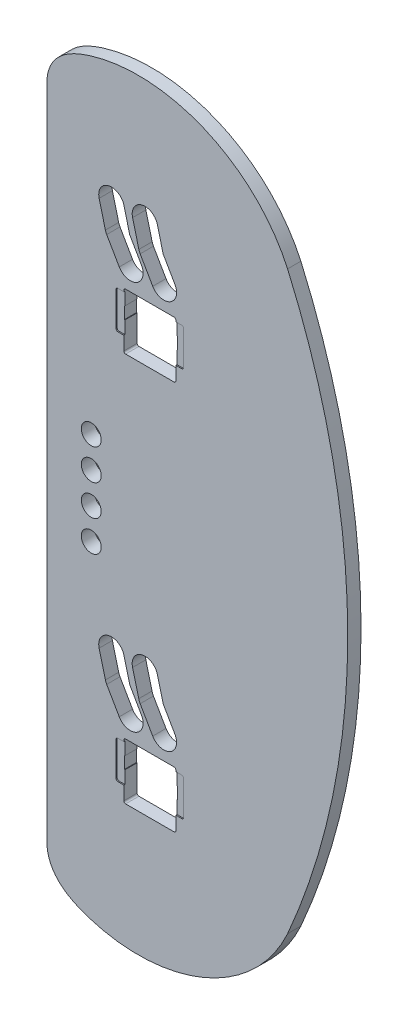
SolidWorks part; units mm, degrees
material "Pine"
ref_plane "Front Plane" through (0, 0, 0) normal (0, 0, 1) x (1, 0, 0)
ref_plane "Top Plane" through (0, 0, 0) normal (0, 1, 0) x (1, 0, 0)
ref_plane "Right Plane" through (0, 0, 0) normal (1, 0, 0) x (0, 0, -1)
sketch "Sketch1" plane through (0, 0, 0) normal (0, 1, 0) x (1, 0, 0)
  line L0 (-92.9216, 89.0184) -> (669.0784, 89.0184)
  line L1 (669.0784, 89.0184) -> (669.0784, 419.2184)
  line L2 (-92.9216, 89.0184) -> (-92.9216, 419.2184)
  line L5 (110.2784, 495.4184) -> (465.8784, 495.4184)
  line L8 (110.2784, 495.4184) -> (-92.9216, 419.2184)
  line L9 (465.8784, 495.4184) -> (669.0784, 419.2184)
  line L10 (-92.9216, 495.4184) -> (669.0784, 495.4184) construction
sketch "Sketch2" plane through (0, 0, 0) normal (0, 0, 1) x (1, 0, 0)
  line L95 (1361.0966, 1819.7347) -> (1361.0966, 996.3635)
  arc A0 (1691.2966, 1027.0491) -> (1691.2966, 1789.0491) centre (733.0004, 1408.0491) ccw
  spline S0 degree 3 poles (1691.2966, 1027.0491) (1656.7077, 922.0591) (1371.3251, 886.2968) (1361.0966, 996.3635) knots 0 0 0 0 7.629784 7.629784 7.629784 7.629784
  spline S1 degree 3 poles (1691.2966, 1789.0491) (1656.7629, 1894.0573) (1371.3251, 1929.8013) (1361.0966, 1819.7347) knots 0 0 0 0 7.638295 7.638295 7.638295 7.638295
sketch "Sketch5" plane through (0, 0, 0) normal (0, 0, 1) x (1, 0, 0)
  line L0 (1361.0966, 1819.7347) -> (1361.0966, 996.3635)
  line L1 (1361.0966, 1789.0491) -> (1361.0966, 1027.0491)
  line L2 (1540.0357, 1006.8697) -> (1540.0357, 1016.3947)
  line L3 (1486.0607, 1097.3572) -> (1486.0607, 1006.8697) construction
  line L4 (1486.0607, 1102.1197) -> (1486.0607, 1092.5947)
  line L5 (1540.0357, 1006.8697) -> (1540.0357, 1097.3572) construction
  line L6 (1544.7982, 1102.1197) -> (1481.2982, 1102.1197) construction
  line L7 (1486.0607, 1006.8697) -> (1540.0357, 1006.8697)
  line L8 (1479.7107, 1016.3947) -> (1546.3857, 1016.3947)
  line L9 (1546.3857, 1016.3947) -> (1546.3857, 1092.5947)
  line L10 (1546.3857, 1092.5947) -> (1479.7107, 1092.5947)
  line L11 (1479.7107, 1016.3947) -> (1479.7107, 1092.5947)
  line L12 (1540.0357, 1548.8399) -> (1540.0357, 1558.3649)
  line L13 (1486.0607, 1548.8399) -> (1540.0357, 1548.8399)
  line L14 (1546.3857, 1634.5649) -> (1479.7107, 1634.5649)
  line L15 (1486.0607, 1644.0899) -> (1486.0607, 1634.5649)
  line L16 (1479.7107, 1558.3649) -> (1479.7107, 1634.5649)
  line L17 (1540.0357, 1644.0899) -> (1486.0607, 1644.0899)
  line L18 (1479.7107, 1558.3649) -> (1546.3857, 1558.3649)
  line L19 (1546.3857, 1558.3649) -> (1546.3857, 1634.5649)
  line L20 (1540.0357, 1092.5947) -> (1540.0357, 1102.1197)
  line L21 (1486.0607, 1016.3947) -> (1486.0607, 1006.8697)
  line L22 (1540.0357, 1634.5649) -> (1540.0357, 1644.0899)
  line L23 (1486.0607, 1558.3649) -> (1486.0607, 1548.8399)
  line L95 (1361.0966, 1819.7347) -> (1361.0966, 996.3635)
  line L115 (1540.0357, 1102.1197) -> (1486.0607, 1102.1197)
  line L199 (1363.2449, 1823.8418) -> (1361.0966, 1819.7347)
  line L200 (1361.0966, 1819.7347) -> (1361.7967, 1824.3165)
  line L201 (1361.7967, 1824.3165) -> (1363.2449, 1823.8418)
  line L202 (1540.0357, 1097.3572) -> (1486.0607, 1097.3572) construction
  line L203 (1481.2982, 1102.1197) -> (1481.2982, 1006.8697) construction
  line L204 (1544.7982, 1006.8697) -> (1544.7982, 1102.1197) construction
  arc A0 (1691.2966, 1027.0491) -> (1691.2966, 1789.0491) centre (733.0004, 1408.0491) ccw
  circle A1 centre (1506.0488, 1194.0197) radius 15.875
  circle A2 centre (1515.0488, 1159.0198) radius 15.875
  circle A3 centre (1533.0488, 1127.7698) radius 15.875
  circle A4 centre (1467.0488, 1159.0198) radius 15.875
  circle A5 centre (1485.0488, 1127.7698) radius 15.875
  circle A6 centre (1458.0488, 1194.0197) radius 15.875
  circle A7 centre (1513.0482, 1054.4947) radius 12
  circle A8 centre (1506.0488, 1735.9899) radius 15.875
  circle A9 centre (1515.0488, 1700.99) radius 15.875
  circle A10 centre (1533.0488, 1669.74) radius 15.875
  circle A11 centre (1467.0488, 1700.99) radius 15.875
  circle A12 centre (1485.0488, 1669.74) radius 15.875
  circle A13 centre (1458.0488, 1735.9899) radius 15.875
  circle A15 centre (1483.5084, 1375.1967) radius 12
  circle A16 centre (1483.9827, 1438.6917) radius 12
  circle A17 centre (1551.8392, 1408.0266) radius 29.9999
  circle A18 centre (1409.3368, 1408.0266) radius 15.9995
  circle A19 centre (1513.0482, 1596.4649) radius 12
  arc A30 (1539.4945, 1725.9331) -> (1482.0488, 1761.3623) centre (1506.0488, 1735.9899) ccw
  arc A32 (1549.9668, 1700.2938) -> (1539.4945, 1725.9331) centre (1515.0488, 1700.99) ccw
  arc A41 (1509.0488, 1644.3676) -> (1549.9668, 1700.2938) centre (1533.0488, 1669.74) ccw
  arc A46 (1450.1308, 1670.4362) -> (1509.0488, 1644.3676) centre (1485.0488, 1669.74) ccw
  arc A47 (1433.6031, 1711.0467) -> (1450.1308, 1670.4362) centre (1467.0488, 1700.99) ccw
  arc A50 (1482.0488, 1761.3623) -> (1433.6031, 1711.0467) centre (1458.0488, 1735.9899) ccw
  arc A64 (1509.0488, 1102.3974) -> (1549.9668, 1158.3235) centre (1533.0488, 1127.7698) ccw
  arc A66 (1450.1308, 1128.466) -> (1509.0488, 1102.3974) centre (1485.0488, 1127.7698) ccw
  arc A68 (1433.6031, 1169.0765) -> (1450.1308, 1128.466) centre (1467.0488, 1159.0198) ccw
  arc A70 (1539.4945, 1183.9629) -> (1482.0488, 1219.3921) centre (1506.0488, 1194.0197) ccw
  arc A72 (1549.9668, 1158.3235) -> (1539.4945, 1183.9629) centre (1515.0488, 1159.0198) ccw
  arc A73 (1482.0488, 1219.3921) -> (1433.6031, 1169.0765) centre (1458.0488, 1194.0197) ccw
  arc A86 (1474.249, 1382.8299) -> (1489.0021, 1364.5282) centre (1483.5084, 1375.1967) ccw
  arc A89 (1488.8753, 1449.649) -> (1474.6166, 1431.19) centre (1483.9827, 1438.6917) ccw
  arc A97 (1557.861, 1378.6372) -> (1557.0728, 1437.5665) centre (1551.8392, 1408.0266) ccw
  arc A99 (1420.1657, 1419.8299) -> (1400.5179, 1421.402) centre (1409.3362, 1408.0491) ccw
  arc A100 (1402.6554, 1393.5084) -> (1419.641, 1395.8067) centre (1409.3362, 1408.0491) ccw
  spline S0 degree 3 poles (1691.2966, 1027.0491) (1656.7077, 922.0591) (1371.3251, 886.2968) (1361.0966, 996.3635) knots 0 0 0 0 7.629784 7.629784 7.629784 7.629784
  spline S1 degree 3 poles (1691.2966, 1789.0491) (1656.7629, 1894.0573) (1371.3251, 1929.8013) (1361.0966, 1819.7347) knots 0 0 0 0 7.638295 7.638295 7.638295 7.638295
  dimension "D1" = 4.7625
sketch "Sketch8" plane through (0, 0, 0) normal (0, 0, 1) x (1, 0, 0)
  line L2 (1540.0357, 1006.8697) -> (1540.0357, 1016.3947)
  line L3 (1486.0607, 1097.3572) -> (1486.0607, 1006.8697) construction
  line L4 (1486.0607, 1102.1197) -> (1486.0607, 1092.5947)
  line L5 (1540.0357, 1006.8697) -> (1540.0357, 1097.3572) construction
  line L6 (1544.7982, 1102.1197) -> (1481.2982, 1102.1197) construction
  line L7 (1486.0607, 1006.8697) -> (1540.0357, 1006.8697)
  line L8 (1479.7107, 1016.3947) -> (1546.3857, 1016.3947)
  line L9 (1546.3857, 1016.3947) -> (1546.3857, 1092.5947)
  line L10 (1546.3857, 1092.5947) -> (1479.7107, 1092.5947)
  line L11 (1479.7107, 1016.3947) -> (1479.7107, 1092.5947)
  line L12 (1540.0357, 1548.8399) -> (1540.0357, 1558.3649)
  line L13 (1486.0607, 1548.8399) -> (1540.0357, 1548.8399)
  line L14 (1546.3857, 1634.5649) -> (1479.7107, 1634.5649)
  line L15 (1486.0607, 1644.0899) -> (1486.0607, 1634.5649)
  line L16 (1479.7107, 1558.3649) -> (1479.7107, 1634.5649)
  line L17 (1540.0357, 1644.0899) -> (1486.0607, 1644.0899)
  line L18 (1479.7107, 1558.3649) -> (1546.3857, 1558.3649)
  line L19 (1546.3857, 1558.3649) -> (1546.3857, 1634.5649)
  line L20 (1540.0357, 1092.5947) -> (1540.0357, 1102.1197)
  line L21 (1486.0607, 1016.3947) -> (1486.0607, 1006.8697)
  line L22 (1540.0357, 1634.5649) -> (1540.0357, 1644.0899)
  line L23 (1486.0607, 1558.3649) -> (1486.0607, 1548.8399)
  line L95 (1361.0966, 1819.7347) -> (1361.0966, 996.3635)
  line L115 (1540.0357, 1102.1197) -> (1486.0607, 1102.1197)
  line L202 (1540.0357, 1097.3572) -> (1486.0607, 1097.3572) construction
  line L203 (1481.2982, 1102.1197) -> (1481.2982, 1006.8697) construction
  line L204 (1544.7982, 1006.8697) -> (1544.7982, 1102.1197) construction
  arc A0 (1691.2966, 1027.0491) -> (1691.2966, 1789.0491) centre (733.0004, 1408.0491) ccw
  circle A1 centre (1506.0488, 1194.0197) radius 15.875
  circle A2 centre (1515.0488, 1159.0198) radius 15.875
  circle A3 centre (1533.0488, 1127.7698) radius 15.875
  circle A4 centre (1467.0488, 1159.0198) radius 15.875
  circle A5 centre (1485.0488, 1127.7698) radius 15.875
  circle A6 centre (1458.0488, 1194.0197) radius 15.875
  circle A7 centre (1513.0482, 1054.4947) radius 12
  circle A8 centre (1506.0488, 1735.9899) radius 15.875
  circle A9 centre (1515.0488, 1700.99) radius 15.875
  circle A10 centre (1533.0488, 1669.74) radius 15.875
  circle A11 centre (1467.0488, 1700.99) radius 15.875
  circle A12 centre (1485.0488, 1669.74) radius 15.875
  circle A13 centre (1458.0488, 1735.9899) radius 15.875
  circle A15 centre (1483.5084, 1375.1967) radius 12
  circle A16 centre (1483.9827, 1438.6917) radius 12
  circle A17 centre (1551.8392, 1408.0266) radius 29.9999
  circle A18 centre (1409.3368, 1408.0266) radius 15.9995
  circle A19 centre (1513.0482, 1596.4649) radius 12
  arc A30 (1539.4945, 1725.9331) -> (1482.0488, 1761.3623) centre (1506.0488, 1735.9899) ccw
  arc A32 (1549.9668, 1700.2938) -> (1539.4945, 1725.9331) centre (1515.0488, 1700.99) ccw
  arc A41 (1509.0488, 1644.3676) -> (1549.9668, 1700.2938) centre (1533.0488, 1669.74) ccw
  arc A46 (1450.1308, 1670.4362) -> (1509.0488, 1644.3676) centre (1485.0488, 1669.74) ccw
  arc A47 (1433.6031, 1711.0467) -> (1450.1308, 1670.4362) centre (1467.0488, 1700.99) ccw
  arc A50 (1482.0488, 1761.3623) -> (1433.6031, 1711.0467) centre (1458.0488, 1735.9899) ccw
  arc A64 (1509.0488, 1102.3974) -> (1549.9668, 1158.3235) centre (1533.0488, 1127.7698) ccw
  arc A66 (1450.1308, 1128.466) -> (1509.0488, 1102.3974) centre (1485.0488, 1127.7698) ccw
  arc A68 (1433.6031, 1169.0765) -> (1450.1308, 1128.466) centre (1467.0488, 1159.0198) ccw
  arc A70 (1539.4945, 1183.9629) -> (1482.0488, 1219.3921) centre (1506.0488, 1194.0197) ccw
  arc A72 (1549.9668, 1158.3235) -> (1539.4945, 1183.9629) centre (1515.0488, 1159.0198) ccw
  arc A73 (1482.0488, 1219.3921) -> (1433.6031, 1169.0765) centre (1458.0488, 1194.0197) ccw
  arc A86 (1474.249, 1382.8299) -> (1489.0021, 1364.5282) centre (1483.5084, 1375.1967) ccw
  arc A89 (1488.8753, 1449.649) -> (1474.6166, 1431.19) centre (1483.9827, 1438.6917) ccw
  arc A97 (1557.861, 1378.6372) -> (1557.0728, 1437.5665) centre (1551.8392, 1408.0266) ccw
  arc A99 (1420.1657, 1419.8299) -> (1400.5179, 1421.402) centre (1409.3362, 1408.0491) ccw
  arc A100 (1402.6554, 1393.5084) -> (1419.641, 1395.8067) centre (1409.3362, 1408.0491) ccw
  spline S0 degree 3 poles (1691.2966, 1027.0491) (1656.7077, 922.0591) (1371.3251, 886.2968) (1361.0966, 996.3635) knots 0 0 0 0 7.629784 7.629784 7.629784 7.629784
  spline S1 degree 3 poles (1691.2966, 1789.0491) (1656.7629, 1894.0573) (1371.3251, 1929.8013) (1361.0966, 1819.7347) knots 0 0 0 0 7.638295 7.638295 7.638295 7.638295
  dimension "D1" = 4.7625
sketch "Sketch9" plane through (0, 0, 0) normal (0, 0, 1) x (1, 0, 0)
  line L0 (1361.0966, 1884.2991) -> (1361.0966, 1060.9279)
  line L1 (1361.0966, 1472.6135) -> (1839.973, 1472.6135)
  circle A20 centre (1506.0488, 1272.2885) radius 12
  circle A21 centre (1515.0488, 1237.2885) radius 12
  circle A22 centre (1533.0488, 1206.0385) radius 12
  circle A23 centre (1467.0488, 1237.2885) radius 12
  circle A24 centre (1485.0488, 1206.0385) radius 12
  circle A25 centre (1458.0488, 1272.2885) radius 12
  circle A26 centre (1513.0482, 1142.2885) radius 12
  circle A27 centre (1501.6642, 1830.4221) radius 12
  circle A28 centre (1510.6642, 1795.4221) radius 12
  circle A29 centre (1528.6642, 1764.1721) radius 12
  circle A31 centre (1462.6642, 1795.4221) radius 12
  circle A33 centre (1480.6642, 1764.1721) radius 12
  circle A34 centre (1453.6642, 1830.4221) radius 12
  circle A35 centre (1508.6636, 1700.4221) radius 12
sketch "Sketch13" plane through (0, 0, 0) normal (0, 0, 1) x (1, 0, 0)
  line L0 (1439.599, 1277.0692) -> (1448.5991, 1242.0693)
  line L1 (1450.5414, 1237.3053) -> (1468.5414, 1206.0553)
  line L2 (1540.0357, 1097.2035) -> (1540.0357, 1104.1885)
  line L3 (1486.0607, 1185.151) -> (1486.0607, 1006.8697) construction
  line L4 (1486.0607, 1187.3735) -> (1486.0607, 1180.3885)
  line L5 (1540.0357, 1006.8697) -> (1540.0357, 1185.151) construction
  line L6 (1544.7982, 1189.9135) -> (1481.2982, 1189.9135) construction
  line L7 (1488.6007, 1094.6635) -> (1537.4957, 1094.6635)
  line L8 (1482.2507, 1104.1885) -> (1543.8457, 1104.1885)
  line L9 (1546.3857, 1106.7285) -> (1546.3857, 1177.8485)
  line L10 (1543.8457, 1180.3885) -> (1482.2507, 1180.3885)
  line L11 (1479.7107, 1106.7285) -> (1479.7107, 1177.8485)
  line L12 (1540.0357, 1656.0035) -> (1540.0357, 1662.9885)
  line L13 (1488.6007, 1653.4635) -> (1537.4957, 1653.4635)
  line L14 (1543.8457, 1739.1885) -> (1482.2507, 1739.1885)
  line L15 (1486.0607, 1746.1735) -> (1486.0607, 1739.1885)
  line L16 (1479.7107, 1665.5285) -> (1479.7107, 1736.6485)
  line L17 (1537.4957, 1748.7135) -> (1488.6007, 1748.7135)
  line L18 (1482.2507, 1662.9885) -> (1543.8457, 1662.9885)
  line L19 (1546.3857, 1665.5285) -> (1546.3857, 1736.6485)
  line L20 (1540.0357, 1180.3885) -> (1540.0357, 1187.3735)
  line L21 (1486.0607, 1104.1885) -> (1486.0607, 1097.2035)
  line L22 (1540.0357, 1739.1885) -> (1540.0357, 1746.1735)
  line L23 (1486.0607, 1662.9885) -> (1486.0607, 1656.0035)
  line L24 (1485.0488, 1196.5135) -> (1533.0488, 1196.5135)
  line L25 (1550.8991, 1222.2168) -> (1533.383, 1252.007)
  line L26 (1524.4986, 1286.5577) -> (1533.383, 1252.007)
  line L27 (1459.748, 1300.7875) -> (1504.3496, 1300.7875)
  line L28 (1439.599, 1835.8692) -> (1448.5991, 1800.8693)
  line L29 (1450.5414, 1796.1053) -> (1468.5414, 1764.8553)
  line L30 (1485.0488, 1755.3135) -> (1533.0488, 1755.3135)
  line L31 (1549.5562, 1783.8718) -> (1532.852, 1812.8721)
  line L32 (1524.4986, 1845.3577) -> (1532.852, 1812.8721)
  line L33 (1458.0488, 1859.6635) -> (1506.0488, 1859.6635)
  line L34 (1513.0482, 1748.7135) -> (1513.0482, 1755.3135)
  line L38 (1513.0482, 1189.9135) -> (1513.0482, 1196.5135)
  line L95 (1361.0966, 1948.8635) -> (1361.0966, 996.3635)
  line L115 (1537.4957, 1189.9135) -> (1488.6007, 1189.9135)
  line L202 (1540.0357, 1185.151) -> (1486.0607, 1185.151) construction
  line L203 (1481.2982, 1189.9135) -> (1481.2982, 1006.8697) construction
  line L204 (1544.7982, 1006.8697) -> (1544.7982, 1189.9135) construction
  arc A0 (1691.2966, 1027.0491) -> (1691.2966, 1918.1779) centre (761.2616, 1472.6135) ccw
  arc A1 (1524.4986, 1286.5577) -> (1504.3496, 1300.7875) centre (1506.0488, 1281.8135) ccw
  arc A2 (1479.7107, 1177.8485) -> (1482.2507, 1180.3885) centre (1482.2507, 1177.8485) cw
  arc A3 (1533.0488, 1196.5135) -> (1547.5414, 1227.9274) centre (1533.0488, 1215.5635) ccw
  arc A4 (1448.5991, 1242.0693) -> (1450.5414, 1237.3053) centre (1467.0488, 1246.8135) ccw
  arc A5 (1468.5414, 1206.0553) -> (1485.0488, 1196.5135) centre (1485.0488, 1215.5635) ccw
  arc A6 (1459.748, 1300.7875) -> (1439.599, 1277.0692) centre (1458.0488, 1281.8135) ccw
  circle A7 centre (1513.0482, 1142.2885) radius 12
  arc A8 (1524.4986, 1845.3577) -> (1506.0488, 1859.6635) centre (1506.0488, 1840.6135) ccw
  arc A9 (1546.3857, 1177.8485) -> (1543.8457, 1180.3885) centre (1543.8457, 1177.8485) ccw
  arc A10 (1533.0488, 1755.3135) -> (1549.5562, 1783.8718) centre (1533.0488, 1774.3635) ccw
  arc A11 (1448.5991, 1800.8693) -> (1450.5414, 1796.1053) centre (1467.0488, 1805.6135) ccw
  arc A12 (1543.8457, 1104.1885) -> (1546.3857, 1106.7285) centre (1543.8457, 1106.7285) ccw
  arc A13 (1458.0488, 1859.6635) -> (1439.599, 1835.8692) centre (1458.0488, 1840.6135) ccw
  arc A14 (1482.2507, 1104.1885) -> (1479.7107, 1106.7285) centre (1482.2507, 1106.7285) cw
  arc A15 (1488.6007, 1094.6635) -> (1486.0607, 1097.2035) centre (1488.6007, 1097.2035) cw
  arc A16 (1537.4957, 1094.6635) -> (1540.0357, 1097.2035) centre (1537.4957, 1097.2035) ccw
  arc A17 (1479.7107, 1736.6485) -> (1482.2507, 1739.1885) centre (1482.2507, 1736.6485) cw
  arc A18 (1546.3857, 1736.6485) -> (1543.8457, 1739.1885) centre (1543.8457, 1736.6485) ccw
  circle A19 centre (1513.0482, 1701.0885) radius 12
  arc A20 (1468.5414, 1764.8553) -> (1485.0488, 1755.3135) centre (1485.0488, 1774.3635) ccw
  arc A21 (1540.0357, 1746.1735) -> (1537.4957, 1748.7135) centre (1537.4957, 1746.1735) ccw
  arc A22 (1486.0607, 1746.1735) -> (1488.6007, 1748.7135) centre (1488.6007, 1746.1735) cw
  arc A23 (1543.8457, 1662.9885) -> (1546.3857, 1665.5285) centre (1543.8457, 1665.5285) ccw
  arc A24 (1537.4957, 1653.4635) -> (1540.0357, 1656.0035) centre (1537.4957, 1656.0035) ccw
  arc A25 (1488.6007, 1653.4635) -> (1486.0607, 1656.0035) centre (1488.6007, 1656.0035) cw
  arc A26 (1479.7107, 1665.5285) -> (1482.2507, 1662.9885) centre (1482.2507, 1665.5285) ccw
  arc A27 (1540.0357, 1187.3735) -> (1537.4957, 1189.9135) centre (1537.4957, 1187.3735) ccw
  arc A28 (1486.0607, 1187.3735) -> (1488.6007, 1189.9135) centre (1488.6007, 1187.3735) cw
  circle A29 centre (1424.5966, 1539.2885) radius 15.875
  circle A30 centre (1424.5966, 1494.8385) radius 15.875
  circle A31 centre (1424.5966, 1450.3885) radius 15.875
  circle A32 centre (1424.5966, 1405.9385) radius 15.875
  spline S0 degree 3 poles (1691.2966, 1027.0491) (1656.7077, 922.0591) (1371.3251, 886.2968) (1361.0966, 996.3635) knots 0 0 0 0 7.629784 7.629784 7.629784 7.629784
  spline S1 degree 3 poles (1691.2966, 1918.1779) (1656.7629, 2023.1861) (1371.3251, 2058.9302) (1361.0966, 1948.8635) knots 0 0 0 0 7.638295 7.638295 7.638295 7.638295
  dimension "D2" = 2.54
  dimension "D4" = 2.54
  dimension "D5" = 2.54
  dimension "D6" = 2.54
  dimension "D7" = 2.54
  dimension "D8" = 2.54
  dimension "D9" = 2.54
  dimension "D3" = 2.54
  dimension "D15" = 2.54
  dimension "D1" = 4.7625
sketch "Sketch19" plane through (0, 0, 0) normal (0, 0, 1) x (1, 0, 0)
  line L0 (1435.8931, 1279.2446) -> (1444.8931, 1244.2446)
  line L1 (1446.7641, 1239.6556) -> (1464.7641, 1208.4056)
  line L2 (1435.8931, 1838.0446) -> (1444.8931, 1803.0447)
  line L3 (1446.7641, 1798.4557) -> (1464.7641, 1767.2057)
  line L4 (1544.5658, 1226.7235) -> (1527.9867, 1255.5065)
  line L5 (1545.9706, 1107.3008) -> (1545.9706, 1145.0833)
  line L6 (1519.4367, 1288.3844) -> (1527.7277, 1256.1417)
  line L7 (1470.5644, 1145.0833) -> (1470.5644, 1162.5458)
  line L8 (1483.8946, 1279.2387) -> (1493.0723, 1243.5972)
  line L9 (1462.7856, 1180.802) -> (1554.5431, 1180.802)
  line L10 (1470.5644, 1162.5458) -> (1471.3581, 1162.5458)
  line L11 (1545.9706, 1162.5458) -> (1546.7644, 1162.5458)
  line L12 (1494.764, 1239.6557) -> (1512.764, 1208.4057)
  line L13 (1471.4367, 1288.3844) -> (1479.7345, 1256.1153)
  line L14 (1470.5644, 1721.3458) -> (1471.3581, 1721.3458)
  line L15 (1460.2456, 1178.262) -> (1460.2456, 1129.367)
  line L16 (1470.5644, 1703.8833) -> (1471.3581, 1703.8833)
  line L17 (1479.9868, 1814.3065) -> (1496.5658, 1785.5234)
  line L18 (1471.3581, 1666.1008) -> (1471.3581, 1703.8833)
  line L19 (1471.4368, 1847.1844) -> (1479.7278, 1814.9417)
  line L20 (1497.4224, 1225.0419) -> (1479.9903, 1255.4858)
  line L21 (1557.0831, 1178.262) -> (1557.0831, 1129.367)
  line L22 (1470.5644, 1145.0833) -> (1471.3581, 1145.0833)
  line L23 (1483.8931, 1838.0446) -> (1492.8931, 1803.0447)
  line L24 (1494.764, 1798.4557) -> (1512.764, 1767.2057)
  line L25 (1527.9867, 1814.3065) -> (1544.5658, 1785.5235)
  line L26 (1462.7856, 1126.827) -> (1554.5431, 1126.827)
  line L27 (1527.7277, 1814.9417) -> (1519.4367, 1847.1844)
  line L28 (1471.3581, 1107.3008) -> (1471.3581, 1145.0833)
  line L29 (1557.0831, 1737.062) -> (1557.0831, 1688.167)
  line L30 (1462.7856, 1739.602) -> (1554.5431, 1739.602)
  line L31 (1471.3581, 1162.5458) -> (1471.3581, 1182.8658)
  line L32 (1545.9706, 1162.5458) -> (1545.9706, 1182.8658)
  line L33 (1545.9706, 1666.1008) -> (1545.9706, 1703.8833)
  line L34 (1473.8981, 1744.2058) -> (1543.4306, 1744.2058)
  line L35 (1473.8981, 1663.5608) -> (1543.4306, 1663.5608)
  line L36 (1546.7644, 1703.8833) -> (1546.7644, 1721.3458)
  line L37 (1470.5644, 1703.8833) -> (1470.5644, 1721.3458)
  line L38 (1545.9706, 1721.3458) -> (1546.7644, 1721.3458)
  line L39 (1545.9706, 1145.0833) -> (1546.7644, 1145.0833)
  line L40 (1460.2456, 1737.062) -> (1460.2456, 1688.167)
  line L41 (1473.8981, 1104.7608) -> (1543.4306, 1104.7608)
  line L42 (1462.7856, 1685.627) -> (1554.5431, 1685.627)
  line L43 (1546.7644, 1145.0833) -> (1546.7644, 1162.5458)
  line L44 (1473.8981, 1185.4058) -> (1543.4306, 1185.4058)
  line L48 (1545.9706, 1721.3458) -> (1545.9706, 1741.6658)
  line L50 (1471.3581, 1721.3458) -> (1471.3581, 1741.6658)
  line L55 (1545.9706, 1703.8833) -> (1546.7644, 1703.8833)
  line L95 (1361.0966, 1948.8635) -> (1361.0966, 996.3635)
  arc A0 (1706.2361, 1059.6777) -> (1706.2361, 1885.5492) centre (761.2616, 1472.6135) ccw
  arc A1 (1471.4368, 1847.1844) -> (1435.8931, 1838.0446) centre (1453.665, 1842.6145) ccw
  arc A2 (1471.4367, 1288.3844) -> (1435.8931, 1279.2446) centre (1453.6649, 1283.8145) ccw
  circle A3 centre (1510.6649, 1248.8146) radius 12
  arc A4 (1460.2456, 1129.367) -> (1462.7856, 1126.827) centre (1462.7856, 1129.367) ccw
  arc A5 (1444.8931, 1244.2446) -> (1446.7641, 1239.6556) centre (1462.6649, 1248.8145) ccw
  arc A6 (1479.9868, 1814.3065) -> (1479.7278, 1814.9417) centre (1482.1878, 1815.5743) cw
  circle A7 centre (1462.6649, 1248.8145) radius 12
  arc A8 (1464.7641, 1767.2057) -> (1496.5658, 1785.5234) centre (1480.6649, 1776.3646) ccw
  arc A10 (1492.8931, 1803.0447) -> (1494.764, 1798.4557) centre (1510.6649, 1807.6146) ccw
  arc A11 (1460.2456, 1688.167) -> (1462.7856, 1685.627) centre (1462.7856, 1688.167) ccw
  arc A12 (1464.7641, 1208.4056) -> (1495.5958, 1228.2319) centre (1480.665, 1217.5646) ccw
  arc A13 (1519.4367, 1847.1844) -> (1483.8931, 1838.0446) centre (1501.6649, 1842.6145) ccw
  arc A14 (1512.764, 1208.4057) -> (1544.5658, 1226.7235) centre (1528.6649, 1217.5646) ccw
  arc A15 (1545.9706, 1182.8658) -> (1543.4306, 1185.4058) centre (1543.4306, 1182.8658) ccw
  arc A16 (1527.9867, 1255.5065) -> (1527.7277, 1256.1417) centre (1530.1877, 1256.7743) cw
  arc A17 (1473.8981, 1663.5608) -> (1471.3581, 1666.1008) centre (1473.8981, 1666.1008) cw
  arc A18 (1543.4306, 1663.5608) -> (1545.9706, 1666.1008) centre (1543.4306, 1666.1008) ccw
  circle A19 centre (1508.6644, 1712.6145) radius 4.7625
  circle A20 centre (1453.6649, 1283.8145) radius 12
  circle A21 centre (1528.6649, 1217.5646) radius 12
  arc A22 (1460.2456, 1178.262) -> (1462.7856, 1180.802) centre (1462.7856, 1178.262) cw
  arc A23 (1545.9706, 1741.6658) -> (1543.4306, 1744.2058) centre (1543.4306, 1741.6658) ccw
  circle A24 centre (1480.665, 1217.5646) radius 12
  arc A25 (1473.8981, 1104.7608) -> (1471.3581, 1107.3008) centre (1473.8981, 1107.3008) cw
  arc A26 (1471.3581, 1741.6658) -> (1473.8981, 1744.2058) centre (1473.8981, 1741.6658) cw
  arc A27 (1471.3581, 1182.8658) -> (1473.8981, 1185.4058) centre (1473.8981, 1182.8658) cw
  circle A28 centre (1501.6649, 1283.8145) radius 12
  circle A29 centre (1424.5966, 1539.2885) radius 14.2875
  circle A30 centre (1424.5966, 1494.8385) radius 14.2875
  circle A31 centre (1424.5966, 1450.3885) radius 14.2875
  circle A32 centre (1424.5966, 1405.9385) radius 14.2875
  arc A33 (1460.2456, 1737.062) -> (1462.7856, 1739.602) centre (1462.7856, 1737.062) cw
  arc A34 (1554.5431, 1685.627) -> (1557.0831, 1688.167) centre (1554.5431, 1688.167) ccw
  arc A35 (1557.0831, 1737.062) -> (1554.5431, 1739.602) centre (1554.5431, 1737.062) ccw
  arc A36 (1557.0831, 1178.262) -> (1554.5431, 1180.802) centre (1554.5431, 1178.262) ccw
  arc A37 (1543.4306, 1104.7608) -> (1545.9706, 1107.3008) centre (1543.4306, 1107.3008) ccw
  arc A38 (1519.4367, 1288.3844) -> (1483.8946, 1279.2387) centre (1501.6649, 1283.8145) ccw
  circle A39 centre (1508.6644, 1153.8145) radius 4.7625
  circle A40 centre (1501.6649, 1842.6145) radius 12
  circle A41 centre (1510.6649, 1807.6146) radius 12
  circle A42 centre (1528.6649, 1776.3646) radius 12
  circle A43 centre (1462.665, 1807.6146) radius 12
  circle A44 centre (1480.6649, 1776.3646) radius 12
  circle A45 centre (1453.665, 1842.6145) radius 12
  arc A46 (1554.5431, 1126.827) -> (1557.0831, 1129.367) centre (1554.5431, 1129.367) ccw
  circle A48 centre (1462.6649, 1248.8145) radius 18.35 construction
  circle A49 centre (1453.6649, 1283.8145) radius 18.35 construction
  circle A50 centre (1480.665, 1217.5646) radius 18.35 construction
  arc A51 (1479.9903, 1255.4858) -> (1479.7345, 1256.1153) centre (1482.1945, 1256.7479) cw
  circle A52 centre (1528.6649, 1217.5646) radius 18.35 construction
  arc A53 (1512.764, 1767.2057) -> (1544.5658, 1785.5235) centre (1528.6649, 1776.3646) ccw
  circle A54 centre (1501.6649, 1842.6145) radius 18.35 construction
  circle A55 centre (1501.6649, 1283.8145) radius 18.35 construction
  circle A56 centre (1510.6649, 1807.6146) radius 18.35 construction
  arc A57 (1492.7403, 1244.8863) -> (1494.764, 1239.6557) centre (1510.6649, 1248.8146) ccw
  arc A58 (1527.9867, 1814.3065) -> (1527.7277, 1814.9417) centre (1530.1877, 1815.5743) cw
  circle A59 centre (1528.6649, 1776.3646) radius 18.35 construction
  circle A60 centre (1480.6649, 1776.3646) radius 18.35 construction
  arc A61 (1444.8931, 1803.0447) -> (1446.7641, 1798.4557) centre (1462.665, 1807.6146) ccw
  circle A62 centre (1453.665, 1842.6145) radius 18.35 construction
  spline S1 degree 3 poles (1361.0966, 996.3635) (1364.4008, 961.2038) (1498.6132, 888.7647) (1658.3076, 954.5721) (1706.2361, 1059.6777) knots 0 0 0 0 0.219674 1 1 1 1
  spline S2 degree 3 poles (1361.0966, 1948.8635) (1364.4008, 1984.0232) (1498.6132, 2056.4623) (1658.3076, 1990.6549) (1706.2361, 1885.5492) knots 0 0 0 0 0.219674 1 1 1 1
  dimension "D2" = 2.54
  dimension "D4" = 2.54
  dimension "D5" = 2.54
  dimension "D9" = 2.54
  dimension "D3" = 2.54
  dimension "D1" = 2.54
extrude "Boss-Extrude2" add sketch "Sketch19" along normal blind 19.05 contours A0 L95 A33 A29 A30 A31 A32 L21 A36 region at (1559.9496, 1472.1577, 0)
sketch "Sketch20" plane through (0, 0, 0) normal (0, 0, 1) x (1, 0, 0)
  line L0 (1435.8931, 1279.2446) -> (1444.8931, 1244.2446)
  line L1 (1446.7641, 1239.6556) -> (1464.7641, 1208.4056)
  line L2 (1435.8931, 1838.0446) -> (1444.8931, 1803.0447)
  line L3 (1446.7641, 1798.4557) -> (1464.7641, 1767.2057)
  line L4 (1544.5658, 1226.7235) -> (1527.9867, 1255.5065)
  line L5 (1545.9706, 1107.3008) -> (1545.9706, 1145.0833)
  line L6 (1519.4367, 1288.3844) -> (1527.7277, 1256.1417)
  line L7 (1470.5644, 1145.0833) -> (1470.5644, 1162.5458)
  line L8 (1483.8946, 1279.2387) -> (1493.0723, 1243.5972)
  line L9 (1462.7856, 1180.802) -> (1554.5431, 1180.802)
  line L10 (1470.5644, 1162.5458) -> (1471.3581, 1162.5458)
  line L11 (1545.9706, 1162.5458) -> (1546.7644, 1162.5458)
  line L12 (1494.764, 1239.6557) -> (1512.764, 1208.4057)
  line L13 (1471.4367, 1288.3844) -> (1479.7345, 1256.1153)
  line L14 (1470.5644, 1721.3458) -> (1471.3581, 1721.3458)
  line L15 (1460.2456, 1178.262) -> (1460.2456, 1129.367)
  line L16 (1470.5644, 1703.8833) -> (1471.3581, 1703.8833)
  line L17 (1479.9868, 1814.3065) -> (1496.5658, 1785.5234)
  line L18 (1471.3581, 1666.1008) -> (1471.3581, 1703.8833)
  line L19 (1471.4368, 1847.1844) -> (1479.7278, 1814.9417)
  line L20 (1497.4224, 1225.0419) -> (1479.9903, 1255.4858)
  line L21 (1557.0831, 1178.262) -> (1557.0831, 1129.367)
  line L22 (1470.5644, 1145.0833) -> (1471.3581, 1145.0833)
  line L23 (1483.8931, 1838.0446) -> (1492.8931, 1803.0447)
  line L24 (1494.764, 1798.4557) -> (1512.764, 1767.2057)
  line L25 (1527.9867, 1814.3065) -> (1544.5658, 1785.5235)
  line L26 (1462.7856, 1126.827) -> (1554.5431, 1126.827)
  line L27 (1527.7277, 1814.9417) -> (1519.4367, 1847.1844)
  line L28 (1471.3581, 1107.3008) -> (1471.3581, 1145.0833)
  line L29 (1557.0831, 1737.062) -> (1557.0831, 1688.167)
  line L30 (1462.7856, 1739.602) -> (1554.5431, 1739.602)
  line L31 (1471.3581, 1162.5458) -> (1471.3581, 1182.8658)
  line L32 (1545.9706, 1162.5458) -> (1545.9706, 1182.8658)
  line L33 (1545.9706, 1666.1008) -> (1545.9706, 1703.8833)
  line L34 (1473.8981, 1744.2058) -> (1543.4306, 1744.2058)
  line L35 (1473.8981, 1663.5608) -> (1543.4306, 1663.5608)
  line L36 (1546.7644, 1703.8833) -> (1546.7644, 1721.3458)
  line L37 (1470.5644, 1703.8833) -> (1470.5644, 1721.3458)
  line L38 (1545.9706, 1721.3458) -> (1546.7644, 1721.3458)
  line L39 (1545.9706, 1145.0833) -> (1546.7644, 1145.0833)
  line L40 (1460.2456, 1737.062) -> (1460.2456, 1688.167)
  line L41 (1473.8981, 1104.7608) -> (1543.4306, 1104.7608)
  line L42 (1462.7856, 1685.627) -> (1554.5431, 1685.627)
  line L43 (1546.7644, 1145.0833) -> (1546.7644, 1162.5458)
  line L44 (1473.8981, 1185.4058) -> (1543.4306, 1185.4058)
  line L48 (1545.9706, 1721.3458) -> (1545.9706, 1741.6658)
  line L50 (1471.3581, 1721.3458) -> (1471.3581, 1741.6658)
  line L55 (1545.9706, 1703.8833) -> (1546.7644, 1703.8833)
  line L95 (1361.0966, 1948.8635) -> (1361.0966, 996.3635)
  arc A0 (1706.2361, 1059.6777) -> (1706.2361, 1885.5492) centre (761.2616, 1472.6135) ccw
  arc A1 (1471.4368, 1847.1844) -> (1435.8931, 1838.0446) centre (1453.665, 1842.6145) ccw
  arc A2 (1471.4367, 1288.3844) -> (1435.8931, 1279.2446) centre (1453.6649, 1283.8145) ccw
  circle A3 centre (1510.6649, 1248.8146) radius 12
  arc A4 (1460.2456, 1129.367) -> (1462.7856, 1126.827) centre (1462.7856, 1129.367) ccw
  arc A5 (1444.8931, 1244.2446) -> (1446.7641, 1239.6556) centre (1462.6649, 1248.8145) ccw
  arc A6 (1479.9868, 1814.3065) -> (1479.7278, 1814.9417) centre (1482.1878, 1815.5743) cw
  circle A7 centre (1462.6649, 1248.8145) radius 12
  arc A8 (1464.7641, 1767.2057) -> (1496.5658, 1785.5234) centre (1480.6649, 1776.3646) ccw
  arc A10 (1492.8931, 1803.0447) -> (1494.764, 1798.4557) centre (1510.6649, 1807.6146) ccw
  arc A11 (1460.2456, 1688.167) -> (1462.7856, 1685.627) centre (1462.7856, 1688.167) ccw
  arc A12 (1464.7641, 1208.4056) -> (1495.5958, 1228.2319) centre (1480.665, 1217.5646) ccw
  arc A13 (1519.4367, 1847.1844) -> (1483.8931, 1838.0446) centre (1501.6649, 1842.6145) ccw
  arc A14 (1512.764, 1208.4057) -> (1544.5658, 1226.7235) centre (1528.6649, 1217.5646) ccw
  arc A15 (1545.9706, 1182.8658) -> (1543.4306, 1185.4058) centre (1543.4306, 1182.8658) ccw
  arc A16 (1527.9867, 1255.5065) -> (1527.7277, 1256.1417) centre (1530.1877, 1256.7743) cw
  arc A17 (1473.8981, 1663.5608) -> (1471.3581, 1666.1008) centre (1473.8981, 1666.1008) cw
  arc A18 (1543.4306, 1663.5608) -> (1545.9706, 1666.1008) centre (1543.4306, 1666.1008) ccw
  circle A19 centre (1508.6644, 1712.6145) radius 4.7625
  circle A20 centre (1453.6649, 1283.8145) radius 12
  circle A21 centre (1528.6649, 1217.5646) radius 12
  arc A22 (1460.2456, 1178.262) -> (1462.7856, 1180.802) centre (1462.7856, 1178.262) cw
  arc A23 (1545.9706, 1741.6658) -> (1543.4306, 1744.2058) centre (1543.4306, 1741.6658) ccw
  circle A24 centre (1480.665, 1217.5646) radius 12
  arc A25 (1473.8981, 1104.7608) -> (1471.3581, 1107.3008) centre (1473.8981, 1107.3008) cw
  arc A26 (1471.3581, 1741.6658) -> (1473.8981, 1744.2058) centre (1473.8981, 1741.6658) cw
  arc A27 (1471.3581, 1182.8658) -> (1473.8981, 1185.4058) centre (1473.8981, 1182.8658) cw
  circle A28 centre (1501.6649, 1283.8145) radius 12
  circle A29 centre (1424.5966, 1539.2885) radius 15.875
  circle A30 centre (1424.5966, 1494.8385) radius 15.875
  circle A31 centre (1424.5966, 1450.3885) radius 15.875
  circle A32 centre (1424.5966, 1405.9385) radius 15.875
  arc A33 (1460.2456, 1737.062) -> (1462.7856, 1739.602) centre (1462.7856, 1737.062) cw
  arc A34 (1554.5431, 1685.627) -> (1557.0831, 1688.167) centre (1554.5431, 1688.167) ccw
  arc A35 (1557.0831, 1737.062) -> (1554.5431, 1739.602) centre (1554.5431, 1737.062) ccw
  arc A36 (1557.0831, 1178.262) -> (1554.5431, 1180.802) centre (1554.5431, 1178.262) ccw
  arc A37 (1543.4306, 1104.7608) -> (1545.9706, 1107.3008) centre (1543.4306, 1107.3008) ccw
  arc A38 (1519.4367, 1288.3844) -> (1483.8946, 1279.2387) centre (1501.6649, 1283.8145) ccw
  circle A39 centre (1508.6644, 1153.8145) radius 4.7625
  circle A40 centre (1501.6649, 1842.6145) radius 12
  circle A41 centre (1510.6649, 1807.6146) radius 12
  circle A42 centre (1528.6649, 1776.3646) radius 12
  circle A43 centre (1462.665, 1807.6146) radius 12
  circle A44 centre (1480.6649, 1776.3646) radius 12
  circle A45 centre (1453.665, 1842.6145) radius 12
  arc A46 (1554.5431, 1126.827) -> (1557.0831, 1129.367) centre (1554.5431, 1129.367) ccw
  circle A48 centre (1462.6649, 1248.8145) radius 18.35 construction
  circle A49 centre (1453.6649, 1283.8145) radius 18.35 construction
  circle A50 centre (1480.665, 1217.5646) radius 18.35 construction
  arc A51 (1479.9903, 1255.4858) -> (1479.7345, 1256.1153) centre (1482.1945, 1256.7479) cw
  circle A52 centre (1528.6649, 1217.5646) radius 18.35 construction
  arc A53 (1512.764, 1767.2057) -> (1544.5658, 1785.5235) centre (1528.6649, 1776.3646) ccw
  circle A54 centre (1501.6649, 1842.6145) radius 18.35 construction
  circle A55 centre (1501.6649, 1283.8145) radius 18.35 construction
  circle A56 centre (1510.6649, 1807.6146) radius 18.35 construction
  arc A57 (1492.7403, 1244.8863) -> (1494.764, 1239.6557) centre (1510.6649, 1248.8146) ccw
  arc A58 (1527.9867, 1814.3065) -> (1527.7277, 1814.9417) centre (1530.1877, 1815.5743) cw
  circle A59 centre (1528.6649, 1776.3646) radius 18.35 construction
  circle A60 centre (1480.6649, 1776.3646) radius 18.35 construction
  arc A61 (1444.8931, 1803.0447) -> (1446.7641, 1798.4557) centre (1462.665, 1807.6146) ccw
  circle A62 centre (1453.665, 1842.6145) radius 18.35 construction
  spline S1 degree 3 poles (1361.0966, 996.3635) (1364.4008, 961.2038) (1498.6132, 888.7647) (1658.3076, 954.5721) (1706.2361, 1059.6777) knots 0 0 0 0 0.219674 1 1 1 1
  spline S2 degree 3 poles (1361.0966, 1948.8635) (1364.4008, 1984.0232) (1498.6132, 2056.4623) (1658.3076, 1990.6549) (1706.2361, 1885.5492) knots 0 0 0 0 0.219674 1 1 1 1
  dimension "D2" = 2.54
  dimension "D4" = 2.54
  dimension "D5" = 2.54
  dimension "D9" = 2.54
  dimension "D3" = 2.54
  dimension "D1" = 2.54
extrude "Boss-Extrude3" add sketch "Sketch20" along normal blind 17.4625 contours A33 L40 A11 L42 L18 L16 L37 L14 L50 L30 | L29 A35 L30 L48 L38 L36 L55 L33 L42 A34 | A22 L15 A4 L26 L28 L22 L7 L10 L31 L9 | L26 A46 L21 A36 L9 L32 L11 L43 L39 L5 region at (1551.6258, 1153.8145, 0) region at (1465.7029, 1153.8145, 0) region at (1465.7029, 1712.6145, 0) region at (1551.6258, 1712.6145, 0)
